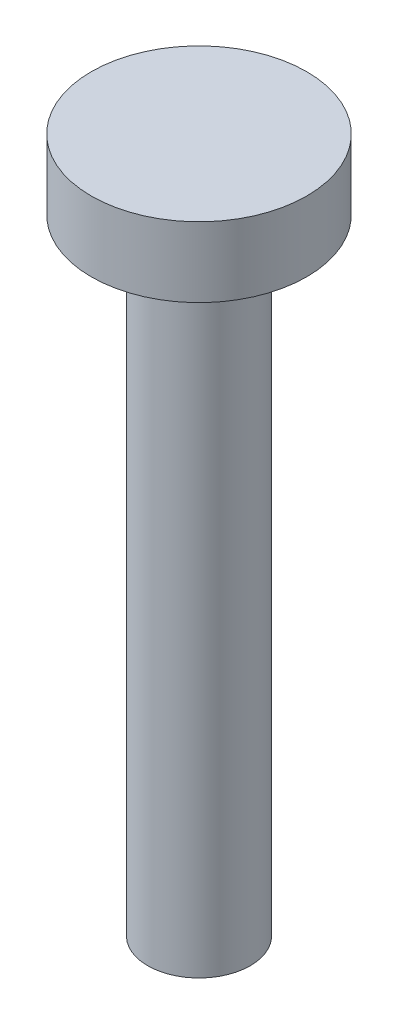
SolidWorks part; units mm, degrees
material "Brass"
ref_plane "Front Plane" through (0, 0, 0) normal (0, 0, 1) x (1, 0, 0)
ref_plane "Top Plane" through (0, 0, 0) normal (0, 1, 0) x (1, 0, 0)
ref_plane "Right Plane" through (0, 0, 0) normal (1, 0, 0) x (0, 0, -1)
sketch "Sketch1" plane through (0, 0, 0) normal (0, 0, 1) x (1, 0, 0)
  line L0 (0, 0) -> (0, 64.5) construction
  line L1 (0, 0) -> (4.7625, 0)
  line L2 (4.7625, 0) -> (4.7625, 58)
  line L3 (4.7625, 58) -> (10, 58)
  line L4 (10, 58) -> (10, 64.5)
  line L5 (10, 64.5) -> (0, 64.5)
  line L6 (0, 64.5) -> (0, 0)
revolve "Revolve1" add sketch "Sketch1" angle 360 about L0
